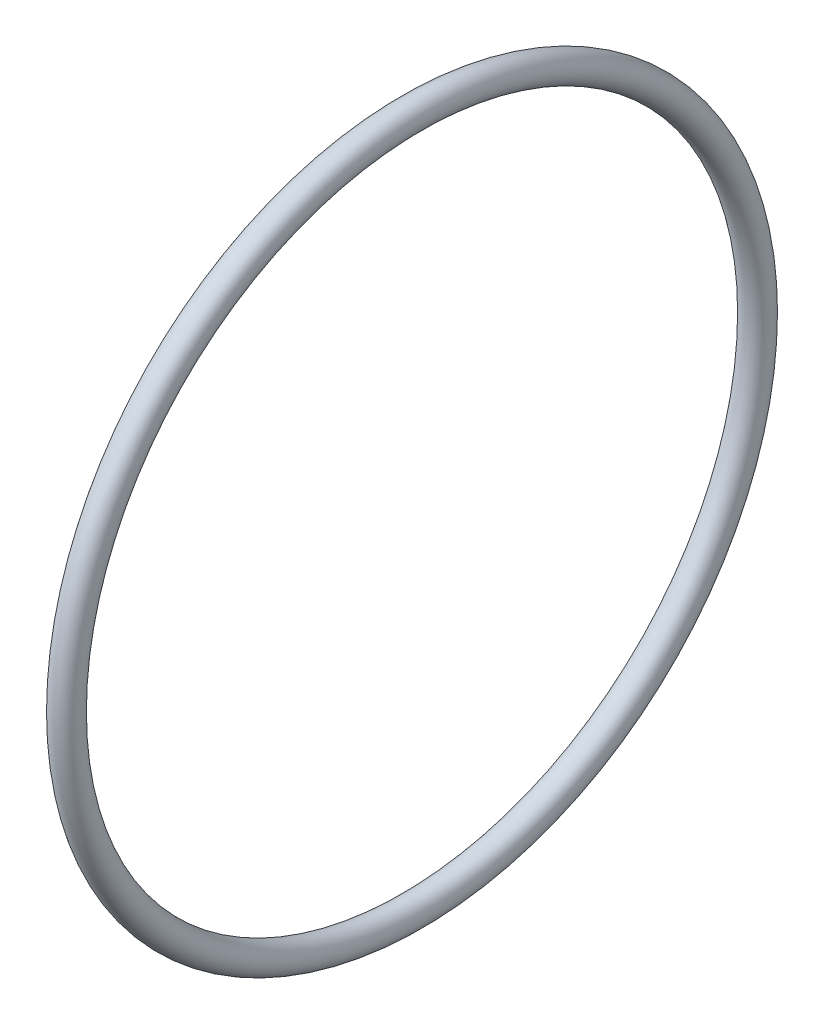
SolidWorks part; units mm, degrees
material "EPICHLOROHYDRIN"
ref_plane "Front Plane" through (0, 0, 0) normal (0, 0, 1) x (1, 0, 0)
ref_plane "Top Plane" through (0, 0, 0) normal (0, 1, 0) x (1, 0, 0)
ref_plane "Right Plane" through (0, 0, 0) normal (1, 0, 0) x (0, 0, -1)
sketch "Sketch1" plane through (0, 0, 0) normal (0, 0, 1) x (1, 0, 0)
  line L0 (-22.1809, 0) -> (22.1809, 0) construction
  circle A0 centre (0, 31.115) radius 1.27
  point P4 (0, 0)
  point P8 (0, 0)
  dimension "D1" = 2.54
  dimension "D2" = 31.115
revolve "Revolve2" add sketch "Sketch1" angle 360 about L0
ref_axis "Axis1" through (-23.1946, 0, 0) along (1, 0, 0)
